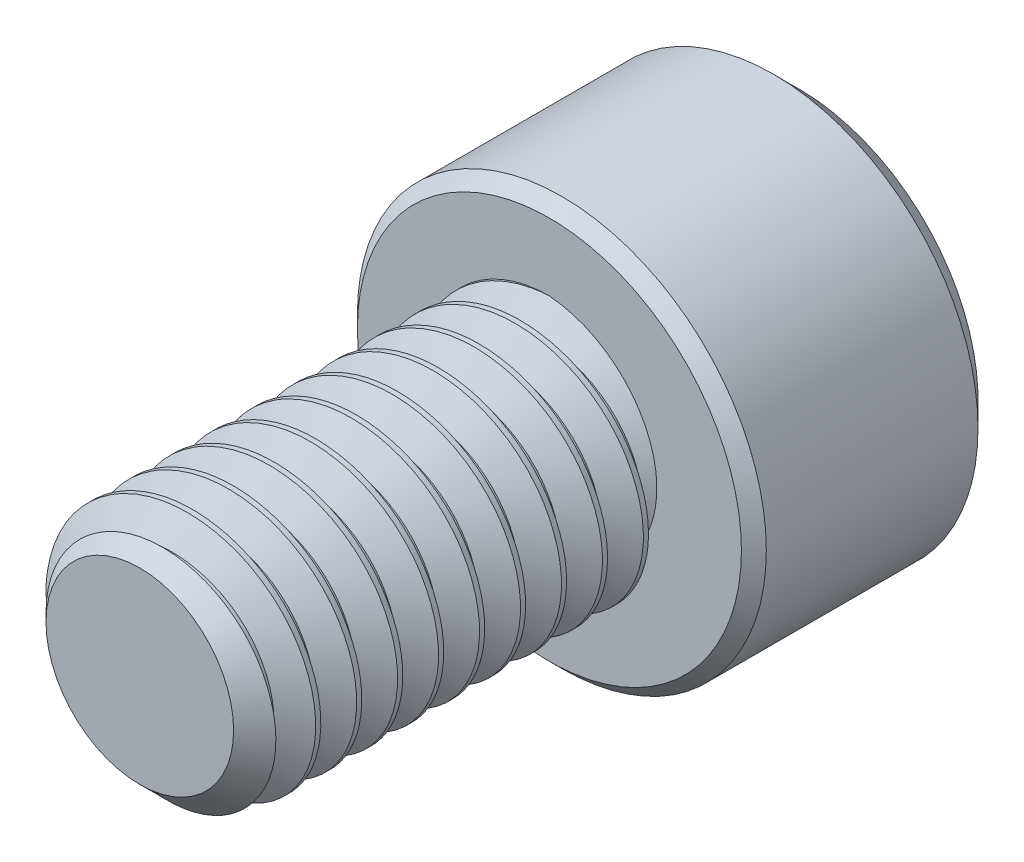
SolidWorks part; units mm, degrees
material "Cast Alloy Steel"
ref_plane "Front Plane" through (0, 0, 0) normal (0, 0, 1) x (1, 0, 0)
ref_plane "Top Plane" through (0, 0, 0) normal (0, 1, 0) x (1, 0, 0)
ref_plane "Right Plane" through (0, 0, 0) normal (1, 0, 0) x (0, 0, -1)
sketch "Sketch1" plane through (0, 0, 0) normal (0, 0, 1) x (1, 0, 0)
  line L0 (0, 2.413) -> (0, -2.413) construction
  circle A0 centre (0, 0) radius 2.413
  dimension "OD" = 4.826
extrude "Extrude1" add sketch "Sketch1" against normal blind 7.9375
sketch "Sketch2" plane through (0, 0, 0) normal (0, 0, 1) x (1, 0, 0)
  circle A0 centre (0, 0) radius 2.413 construction
  circle A1 centre (0, 0) radius 2.413
curve "Helix/Spiral1" pitch 0.7937 height 8.7312 turns 11 parameters "pitch"=0.7937
chamfer "Chamfer3" distance 0.5953 angle 45 1 edges at (2.413, 0, 0)
sketch "Sketch3" plane through (0, 0, 0) normal (1, 0, 0) x (0, 0, -1)
  line L0 (-0.6945, 2.413) -> (-0.3969, 1.8974)
  line L1 (-0.3969, 1.8974) -> (-0.2977, 1.8974)
  line L2 (-0.2977, 1.8974) -> (0, 2.413)
  line L3 (-0.6945, 2.413) -> (0, 2.413)
  line L4 (-0.3473, 2.413) -> (-0.3473, 1.8974) construction
  line L5 (-0.5457, 2.1552) -> (-0.1488, 2.1552) construction
  line L6 (0, 2.413) -> (0, -2.413) construction
  dimension "D1" = 0.0992
  dimension "D2" = 0.3969
  dimension "D3" = 60
sweep "Cut-Sweep1" cut profiles "Sketch3" path "Helix/Spiral1"
sketch "Sketch6" plane through (0, 0, -7.9375) normal (0, 0, -1) x (-1, 0, 0)
  circle A0 centre (0, 0) radius 3.9624
  dimension "head dia" = 7.9248
extrude "Extrude2" add sketch "Sketch6" along normal blind 4.826
sketch "Sketch7" plane through (0, 0, -12.7635) normal (0, 0, -1) x (-1, 0, 0)
  line L1 (0, 2.2914) -> (-1.9844, 1.1457)
  line L2 (-1.9844, 1.1457) -> (-1.9844, -1.1457)
  line L3 (-1.9844, -1.1457) -> (0, -2.2914)
  line L4 (0, -2.2914) -> (1.9844, -1.1457)
  line L5 (1.9844, -1.1457) -> (1.9844, 1.1457)
  line L6 (1.9844, 1.1457) -> (0, 2.2914)
  circle A0 centre (0, 0) radius 1.9844 construction
  dimension "hex dia" = 3.9688
extrude "Cut-Extrude1" cut sketch "Sketch7" against normal blind 2.9766
sketch "Sketch8" plane through (0, 0, -12.7635) normal (0, 0, -1) x (-1, 0, 0)
  circle A0 centre (0, 0) radius 2.2914
extrude "Cut-Extrude2" cut sketch "Sketch8" against normal blind 0.4826 draft 45
chamfer "Chamfer1" distance 0.4826 angle 45 1 edges at (-3.9624, 0, -12.7635)
chamfer "Chamfer2" distance 0.2413 angle 45 1 edges at (-3.9624, 0, -7.9375)
sketch "Sketch9" plane through (0, 0, 0) normal (1, 0, 0) x (0, 0, -1)
  line L0 (0, 2.413) -> (0, -2.413) construction
  line L1 (4.3656, 2.413) -> (4.3656, -2.413) construction
  line L2 (7.9375, 3.9624) -> (7.9375, -3.9624) construction
  line L3 (12.7635, 3.9624) -> (12.7635, -3.9624) construction
  line L4 (12.7635, 0) -> (0, 0) construction
  dimension "D1" = 4.3656
  dimension "D2" = 4.826
  dimension "D3" = 7.9248
  dimension "D4" = 7.9375
equation "\"D3@Helix/Spiral1\" = \"screw length@Extrude1\"+\"pitch@Helix/Spiral1\""
equation "\"D1@Sketch3\" = \"pitch@Helix/Spiral1\"*.125"
equation "\"D2@Sketch3\" = \"pitch@Helix/Spiral1\"*.5"
equation "\"D1@Cut-Extrude1\" = \"hex dia@Sketch7\"*.75"
equation "\"D1@Chamfer1\" = \"head depth@Extrude2\"/10"
equation "\"D1@Sketch9\" = \"pitch@Helix/Spiral1\"*5.5"
equation "\"D1@Chamfer2\" = \"D1@Chamfer1\"/2"
equation "\"D1@Cut-Extrude2\" = \"D1@Chamfer2\"*2"
equation "\"D1@Chamfer3\" = \"pitch@Helix/Spiral1\"*.750"
equation "\"D2@Sketch9\" = \"head depth@Extrude2\""
equation "\"D3@Sketch9\" = \"head dia@Sketch6\""
equation "\"D4@Sketch9\" = \"screw length@Extrude1\""
